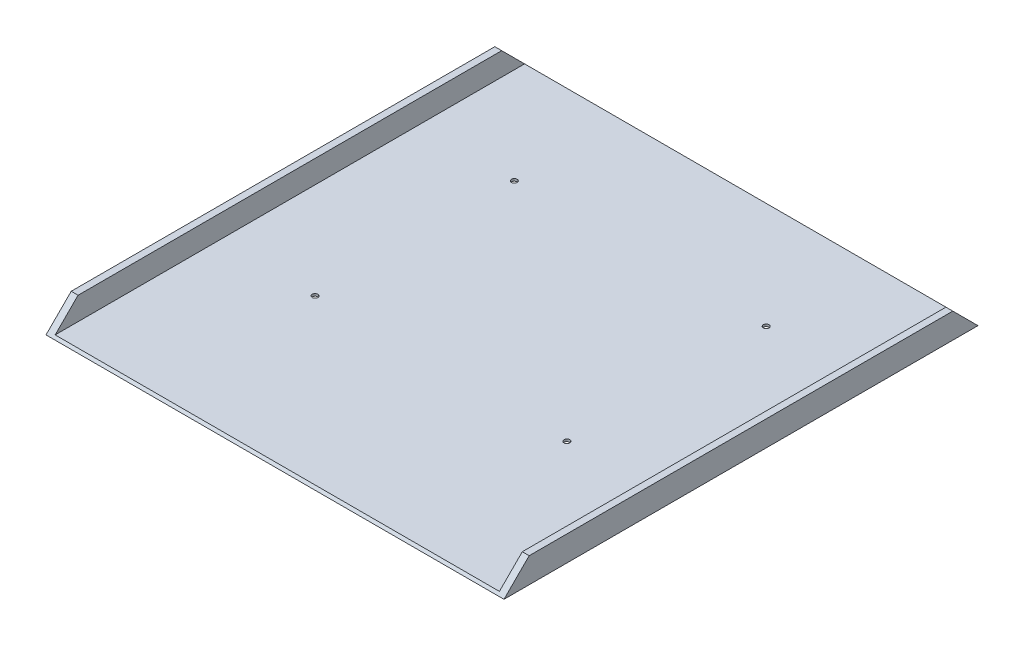
SolidWorks part; units mm, degrees
ref_plane "Front Plane" through (0, 0, 0) normal (0, 0, 1) x (1, 0, 0)
ref_plane "Top Plane" through (0, 0, 0) normal (0, 1, 0) x (1, 0, 0)
ref_plane "Right Plane" through (0, 0, 0) normal (1, 0, 0) x (0, 0, -1)
sketch "Sketch1" plane through (0, 0, 0) normal (0, 1, 0) x (1, 0, 0)
  line L0 (100, 0) -> (100, -225) construction
  line L1 (0, 0) -> (200, 0)
  line L2 (0, 0) -> (0, -225)
  line L3 (0, -225) -> (200, -225)
  line L4 (200, 0) -> (200, -225)
  line L5 (0, -112.5) -> (200, -112.5) construction
  circle A0 centre (45, -56.5) radius 1.25
  circle A1 centre (155, -56.5) radius 1.25
  circle A4 centre (45, -143.5) radius 1.25
  circle A5 centre (155, -143.5) radius 1.25
  dimension "D5" = 2.5
  dimension "D7" = 2.5
  dimension "D1" = 200
  dimension "D2" = 225
  dimension "D3" = 45
  dimension "D4" = 56.5
  dimension "D6" = 81.5
  dimension "D8" = 45
extrude "Boss-Extrude1" add sketch "Sketch1" along normal blind 1
sketch "Sketch2" plane through (0, 1, 0) normal (0, 1, 0) x (1, 0, 0)
  line L5 (0, -225) -> (200, -225) construction
  line L7 (0, 0) -> (3, 0)
  line L8 (0, 0) -> (0, -225)
  line L9 (0, -225) -> (3, -225)
  line L10 (3, 0) -> (3, -225)
  line L12 (200, 0) -> (197, 0)
  line L13 (200, 0) -> (200, -225)
  line L14 (200, -225) -> (197, -225)
  line L15 (197, 0) -> (197, -225)
  dimension "D1" = 3
  dimension "D2" = 3
extrude "Boss-Extrude2" add sketch "Sketch2" along normal blind 10
chamfer "Chamfer7" distance 20 angle 45 1 edges at (1.5, 11, 0)
chamfer "Chamfer8" distance 20 angle 45 1 edges at (1.5, 11, 225)
